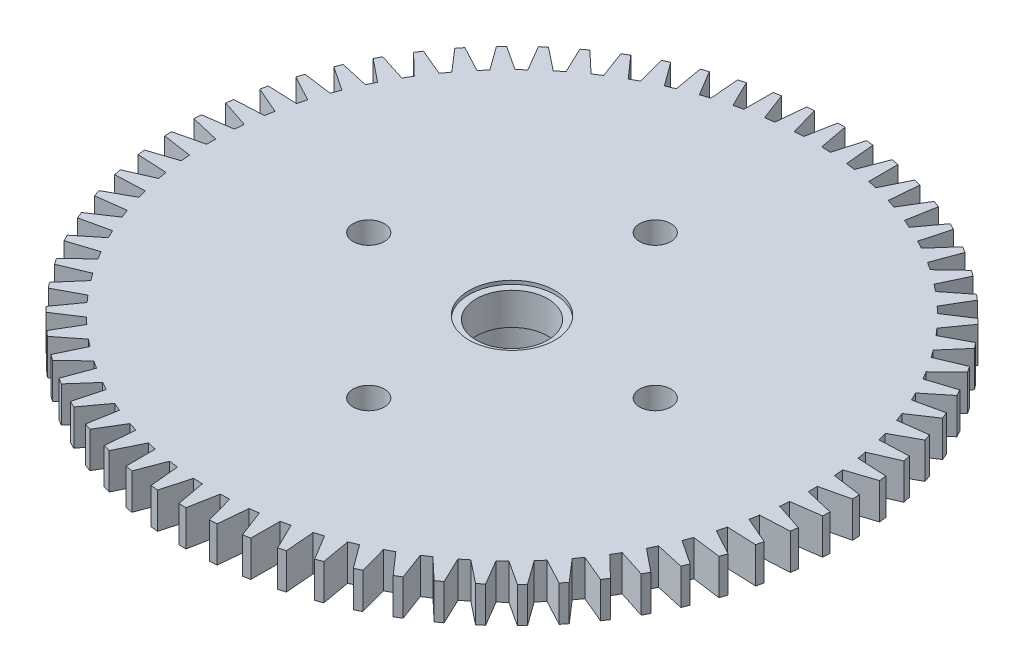
SolidWorks part; units mm, degrees
material "ABS"
ref_plane "Front" through (0, 0, 0) normal (0, 0, 1) x (1, 0, 0)
ref_plane "Top" through (0, 0, 0) normal (0, 1, 0) x (1, 0, 0)
ref_plane "Right" through (0, 0, 0) normal (1, 0, 0) x (0, 0, -1)
sketch "Sketch2" plane through (0, 0, 0) normal (0, 1, 0) x (1, 0, 0)
  circle A0 centre (0, 0) radius 21
  circle A1 centre (0, 0) radius 2.5
  dimension "D1" = 42
  dimension "D2" = 5
extrude "Boss-Extrude1" add sketch "Sketch2" along normal blind 2.5
ref_plane "Plane1" through (0, 0, 0) normal (0, 1, 0) x (1, 0, 0)
sketch "Sketch3" plane through (0, 0, 0) normal (0, 1, 0) x (1, 0, 0)
  line L0 (0, 21) -> (0, -21) construction
  line L1 (-21, 0) -> (21, 0) construction
  line L3 (0, 21) -> (0, 23) construction
  line L4 (-0.625, 20.9907) -> (-0.25, 23)
  line L5 (-0.25, 23) -> (0.25, 23)
  line L6 (0.625, 20.9907) -> (0.25, 23)
  circle A0 centre (0, 0) radius 21 construction
  arc A1 (-21, 0) -> (21, 0) centre (0, 0) ccw
  arc A2 (0.625, 20.9907) -> (-0.625, 20.9907) centre (0, 0) ccw
  dimension "D1" = 1.25
  dimension "D2" = 0.25
  dimension "D3" = 23
extrude "Boss-Extrude2" add sketch "Sketch3" along normal blind 2.5 contours L6 L5 L4 A2
pattern_circular "CirPattern1" count 70 over 360 about axis through (0, 2.5, 0) along (0, 1, 0) of "Boss-Extrude2"
sketch "Sketch4" plane through (0, 2.5, 0) normal (0, 1, 0) x (1, 0, 0)
  circle A0 centre (0, 0) radius 3
  circle A1 centre (0, 0) radius 2.5
  circle A2 centre (0, 0) radius 2.5 construction
  dimension "D1" = 0.5
extrude "Cut-Extrude1" cut sketch "Sketch4" against normal blind 0.25
ref_plane "Plane2" through (0, 2.5, 0) normal (0, 1, 0) x (1, 0, 0)
sketch "Sketch5" plane through (0, 2.5, 0) normal (0, 1, 0) x (1, 0, 0)
  line L0 (-34.259, 0) -> (34.259, 0) construction
  line L1 (0, -34.259) -> (0, 34.259) construction
  circle A0 centre (0, 10) radius 1.09
  point P6 (0, 0)
  dimension "D1" = 10
  dimension "D2" = 2.18
extrude "Cut-Extrude2" cut sketch "Sketch5" against normal up to surface (2.5 mm away) up to face at (0, 0, 0)
pattern_circular "CirPattern2" count 4 over 360 about axis through (0, 2.25, 0) along (0, 1, 0) of "Cut-Extrude2"
sketch "Sketch6" plane through (0, 0, 0) normal (0, -1, 0) x (-1, 0, 0)
  circle A0 centre (0, 0) radius 3.15
  circle A1 centre (0, 0) radius 2.8
  dimension "D1" = 6.3
  dimension "D2" = 5.6
extrude "Boss-Extrude3" add sketch "Sketch6" along normal blind 3
